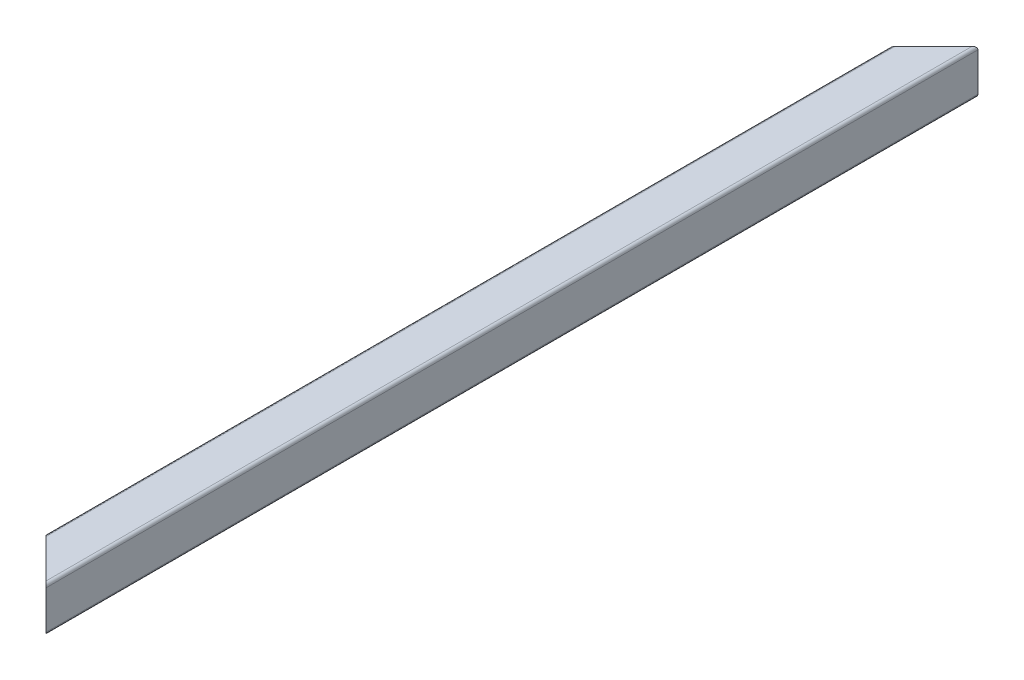
SolidWorks part; units mm, degrees
material "1.4003 (X2CrNi12)"
ref_plane "Ön Düzlem" through (0, 0, 0) normal (0, 0, 1) x (1, 0, 0)
ref_plane "Üst Düzlem" through (0, 0, 0) normal (0, 1, 0) x (1, 0, 0)
ref_plane "Sağ Düzlem" through (0, 0, 0) normal (1, 0, 0) x (0, 0, -1)
sketch "Çizim1" plane through (0, 0, 0) normal (0, 0, 1) x (1, 0, 0)
  line L0 (-13, -13) -> (13, -13)
  line L1 (-13, 15) -> (13, 15)
  line L2 (-15, 13) -> (-15, -13)
  line L3 (-13, -15) -> (13, -15)
  line L4 (15, 13) -> (15, -13)
  line L5 (-15, 15) -> (15, -15) construction
  line L6 (-15, -15) -> (15, 15) construction
  line L7 (13, 13) -> (13, -13)
  line L8 (-13, 13) -> (13, 13)
  line L9 (-13, 13) -> (-13, -13)
  line L10 (15, 15) -> (15, -15) construction
  line L11 (-15, -15) -> (15, -15) construction
  line L12 (-15, 15) -> (-15, -15) construction
  line L13 (-15, 15) -> (15, 15) construction
  arc A0 (15, -13) -> (13, -15) centre (13, -13) cw
  arc A1 (-15, -13) -> (-13, -15) centre (-13, -13) ccw
  arc A2 (13, 15) -> (15, 13) centre (13, 13) cw
  arc A3 (-13, 15) -> (-15, 13) centre (-13, 13) ccw
  point P0 (0, 0)
  dimension "D4" = 2
  dimension "D1" = 30
  dimension "D2" = 30
  dimension "D3" = 2
extrude "Yükseklik-Ekstrüzyon1" add sketch "Çizim1" along normal blind 315 and the other way blind 315
sketch "Çizim2" plane through (0, 0, 0) normal (0, 1, 0) x (1, 0, 0)
  line L0 (15, 315) -> (-15, 285)
  line L1 (-15, 315) -> (-15, -315) construction
  line L2 (-15, 285) -> (-15, 315)
  line L3 (-15, 315) -> (15, 315)
  line L4 (15, -315) -> (-15, -285)
  line L5 (-15, -285) -> (-15, -315)
  line L6 (-15, -315) -> (15, -315)
  dimension "D1" = 45
  dimension "D2" = 45
extrude "Kes-Ekstrüzyon1" cut sketch "Çizim2" against normal blind 250 and the other way blind 250
